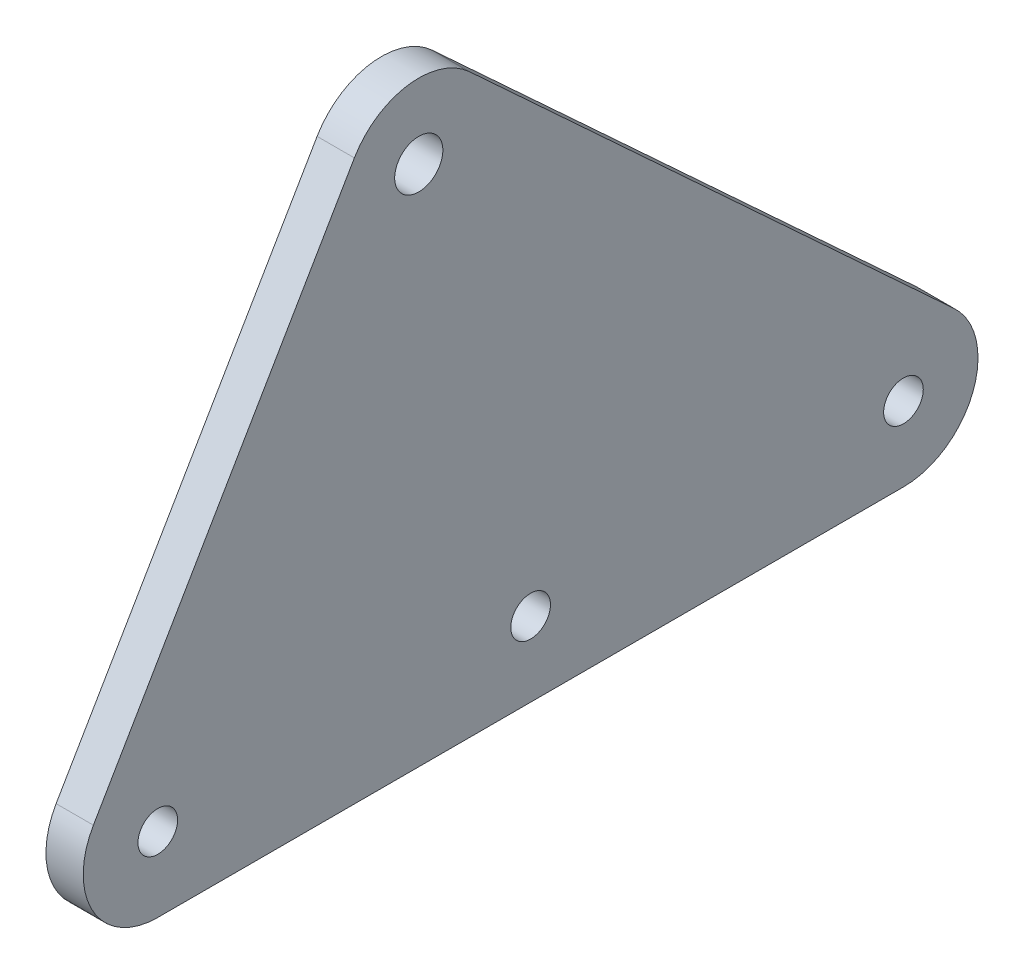
SolidWorks part; units mm, degrees
ref_plane "Front Plane" through (0, 0, 0) normal (0, 0, 1) x (1, 0, 0)
ref_plane "Top Plane" through (0, 0, 0) normal (0, 1, 0) x (1, 0, 0)
ref_plane "Right Plane" through (0, 0, 0) normal (1, 0, 0) x (0, 0, -1)
sketch "Sketch1" plane through (0, 0, 0) normal (1, 0, 0) x (0, 0, -1)
  line L0 (-55.42, -69.8008) -> (-10.97, 6.3992)
  line L1 (8.6142, 9.332) -> (91.1642, -66.868)
  line L2 (-44.45, -88.9) -> (82.55, -88.9)
  arc A0 (8.6142, 9.332) -> (-10.97, 6.3992) centre (0, 0) ccw
  arc A1 (82.55, -88.9) -> (91.1642, -66.868) centre (82.55, -76.2) ccw
  arc A2 (-55.42, -69.8008) -> (-44.45, -88.9) centre (-44.45, -76.2) ccw
  dimension "D1" = 127
  dimension "D2" = 76.2
  dimension "D3" = 44.45
  dimension "D4" = 25.4
extrude "Boss-Extrude1" add sketch "Sketch1" along normal blind 6.35 contours L1 A1 L2 A2 L0 A0
sketch "Sketch2" plane through (6.35, 0, 0) normal (1, 0, 0) x (0, 0, -1)
  line L1 (-44.45, -88.9) -> (82.55, -88.9) construction
  circle A0 centre (-44.45, -76.2) radius 3.3782
  circle A1 centre (19.05, -76.2) radius 3.3782
  circle A2 centre (82.55, -76.2) radius 3.3782
  arc A3 (-55.42, -69.8008) -> (-44.45, -88.9) centre (-44.45, -76.2) ccw construction
  arc A4 (82.55, -88.9) -> (91.1642, -66.868) centre (82.55, -76.2) ccw construction
  circle A5 centre (0, 0) radius 4.1021
  dimension "D2" = 0
  dimension "D3" = 0
  dimension "D4" = 63.5
  dimension "D5" = 6.7564
  dimension "D6" = 8.2042
extrude "Cut-Extrude1" cut sketch "Sketch2" against normal up to next
